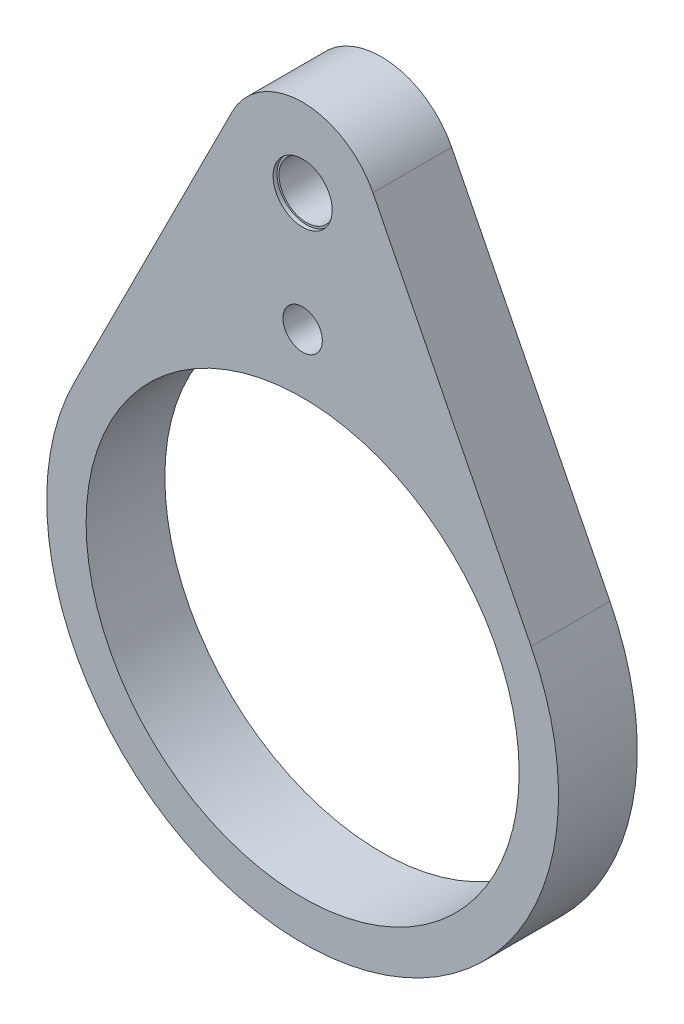
SolidWorks part; units mm, degrees
ref_plane "Front Plane" through (0, 0, 0) normal (0, 0, 1) x (1, 0, 0)
ref_plane "Top Plane" through (0, 0, 0) normal (0, 1, 0) x (1, 0, 0)
ref_plane "Right Plane" through (0, 0, 0) normal (1, 0, 0) x (0, 0, -1)
sketch "Sketch2" plane through (0, 0, 0) normal (0, 0, 1) x (1, 0, 0)
  line L0 (-19.7949, 2.8571) -> (-9.8974, 71.4286)
  line L1 (9.8974, 71.4286) -> (19.7949, 2.8571)
  line L2 (-2.5, 9.6825) -> (-2.5, 12)
  line L3 (-2.5, 12) -> (2.5, 12)
  line L4 (2.5, 12) -> (2.5, 9.6825)
  arc A0 (-19.7949, 2.8571) -> (19.7949, 2.8571) centre (0, 0) ccw
  arc A1 (-2.5, 9.6825) -> (2.5, 9.6825) centre (0, 0) ccw
  arc A2 (9.8974, 71.4286) -> (-9.8974, 71.4286) centre (0, 70) ccw
  circle A3 centre (0, 70) radius 5
  point P12 (0, 12)
  dimension "D1" = 20
  dimension "D2" = 40
  dimension "D3" = 10
  dimension "D4" = 20
  dimension "D5" = 70
  dimension "D6" = 12
  dimension "D7" = 5
extrude "Boss-Extrude1" add sketch "Sketch2" along normal blind 10
sketch "Sketch3" plane through (0, 0, 10) normal (0, 0, 1) x (1, 0, 0)
  circle A0 centre (0, 70) radius 10
  arc A1 (9.8974, 71.4286) -> (-9.8974, 71.4286) centre (0, 70) ccw construction
  circle A2 centre (0, 70) radius 5
  circle A3 centre (0, 70) radius 5 construction
extrude "Boss-Extrude2" add sketch "Sketch3" along normal blind 76.2
extrude "Boss-Extrude3" add sketch "Sketch2<2>" along normal blind 20 from surface starting at face at (10, 70, 86.2)
sketch "Sketch2<2>" plane through (0, 0, 0) normal (0, 0, 1) x (1, 0, 0) same geometry as "Sketch2"
sketch "Sketch5" plane through (0, 0, 106.2) normal (0, 0, 1) x (1, 0, 0)
  circle A0 centre (0, 0) radius 65
  dimension "D1" = 130
extrude "Boss-Extrude4" add sketch "Sketch5" against normal up to surface (20 mm away) up to face at (0, 5.9206, 86.2)
sketch "Sketch6" plane through (0, 0, 106.2) normal (0, 0, 1) x (1, 0, 0)
  circle A0 centre (0, 0) radius 55
  dimension "D1" = 110
extrude "Cut-Extrude1" cut sketch "Sketch6" against normal up to surface (20 mm away) contours A0 up to face at (0, 32.6245, 86.2)
sketch "Sketch7" plane through (0, 0, 86.2) normal (0, 0, -1) x (-1, 0, 0)
  circle A0 centre (0, 0) radius 80
  arc A1 (9.8974, 71.4286) -> (-9.8974, 71.4286) centre (0, 70) ccw construction
extrude "Cut-Extrude2" cut sketch "Sketch7" along normal through all
sketch "Sketch8" plane through (0, 0, 106.2) normal (0, 0, 1) x (1, 0, 0)
  line L0 (-58.0469, 29.25) -> (-17.8606, 109)
  line L1 (58.0469, 29.25) -> (17.8606, 109)
  arc A0 (-10.9596, 64.0694) -> (10.9596, 64.0694) centre (0, 0) ccw construction
  arc A1 (-17.8606, 109) -> (17.8606, 109) centre (0, 100) cw
  arc A2 (-58.0469, 29.25) -> (58.0469, 29.25) centre (0, 0) cw
  arc A3 (9.8974, 71.4286) -> (-9.8974, 71.4286) centre (0, 70) ccw construction
  circle A4 centre (0, 100) radius 7
  circle A5 centre (0, 70) radius 5
  circle A6 centre (0, 70) radius 5 construction
  point P19 (0, 80)
  arc M9 (-10.9596, 64.0694) -> (10.9596, 64.0694) centre (0, 0) ccw
  line M10 (10.9596, 64.0694) -> (9.8974, 71.4286)
  arc M11 (9.8974, 71.4286) -> (-9.8974, 71.4286) centre (0, 70) ccw
  line M12 (-9.8974, 71.4286) -> (-10.9596, 64.0694)
  dimension "D1" = 20
  dimension "D3" = 14
  dimension "D2" = 20
extrude "Boss-Extrude6" add sketch "Sketch8" against normal up to surface (20 mm away) contours A1 L0 L1 A4 M9 M12 M11 M10 region at (0, 82.4331, 106.2) up to face at (55, 0, 86.2)
sketch "Sketch9" plane through (0, 0, 106.2) normal (0, 0, 1) x (1, 0, 0)
  circle A0 centre (0, 100) radius 7.5
  dimension "D1" = 15
extrude "Cut-Extrude3" cut sketch "Sketch9" against normal blind 1
sketch "Sketch10" plane through (0, 0, 86.2) normal (0, 0, -1) x (-1, 0, 0)
  circle A0 centre (0, 100) radius 7.5
  dimension "D1" = 15
extrude "Cut-Extrude4" cut sketch "Sketch10" against normal blind 1
